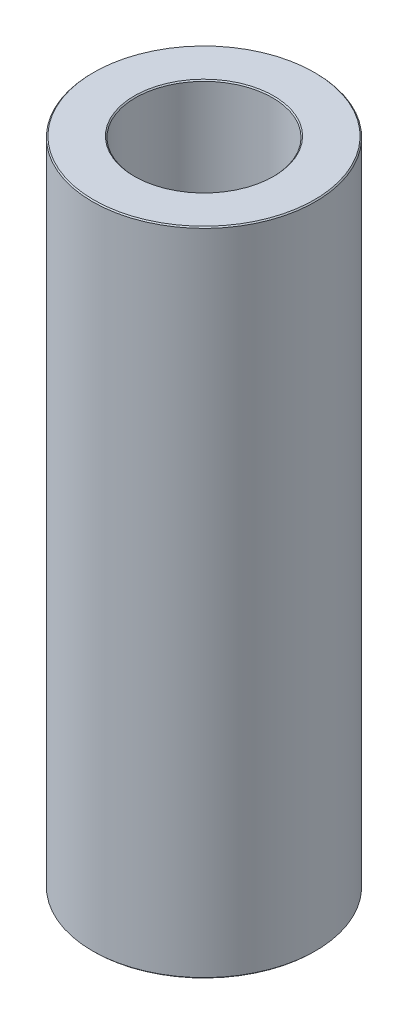
SolidWorks part; units mm, degrees
ref_plane "Front Plane" through (0, 0, 0) normal (0, 0, 1) x (1, 0, 0)
ref_plane "Top Plane" through (0, 0, 0) normal (0, 1, 0) x (1, 0, 0)
ref_plane "Right Plane" through (0, 0, 0) normal (1, 0, 0) x (0, 0, -1)
sketch "Sketch1" plane through (0, 0, 0) normal (0, 1, 0) x (1, 0, 0)
  circle A0 centre (0, 0) radius 32.5
  dimension "SLEEVE_OD" = 65
extrude "Boss-Extrude1" add sketch "Sketch1" along normal blind 189.7842
sketch "Sketch2" plane through (0, 0, 0) normal (0, 1, 0) x (1, 0, 0)
  circle A0 centre (0, 0) radius 20.0091
  dimension "BORE_D" = 40.0183
extrude "Cut-Extrude1" cut sketch "Sketch2" along normal through all
chamfer "Chamfer1" distance 0.3196 angle 45 4 edges at (0, 189.7842, 20.0091) (0, 0, 20.0091) (0, 0, 32.5) (0, 189.7842, 32.5)
